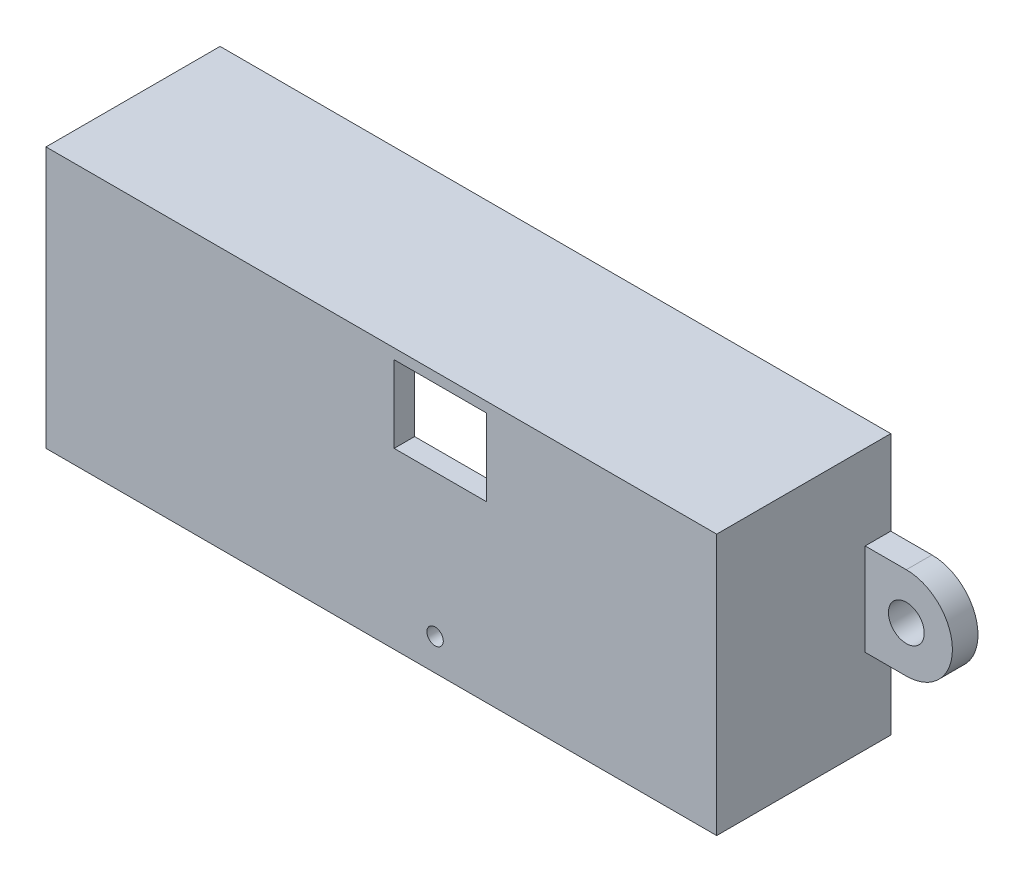
SolidWorks part; units mm, degrees
ref_plane "Спереди" through (0, 0, 0) normal (0, 0, 1) x (1, 0, 0)
ref_plane "Сверху" through (0, 0, 0) normal (0, 1, 0) x (1, 0, 0)
ref_plane "Справа" through (0, 0, 0) normal (1, 0, 0) x (0, 0, -1)
sketch "Эскиз1" plane through (0, 0, 0) normal (0, 0, 1) x (1, 0, 0)
  line L5 (0, 0) -> (123, 0)
  line L6 (0, 0) -> (0, 43)
  line L7 (0, 43) -> (123, 43)
  line L8 (123, 0) -> (123, 43)
  dimension "D1" = 123
  dimension "D2" = 43
extrude "Бобышка-Вытянуть1" add sketch "Эскиз1" along normal blind 4
sketch "Эскиз2" plane through (0, 0, 0) normal (0, 0, -1) x (-1, 0, 0)
  line L1 (-127, -4) -> (4, -4)
  line L2 (-127, -4) -> (-127, 47)
  line L3 (-127, 47) -> (4, 47)
  line L4 (4, -4) -> (4, 47)
  line L9 (-123, 0) -> (0, 0)
  line L10 (-123, 0) -> (-123, 43)
  line L11 (-123, 43) -> (0, 43)
  line L12 (0, 0) -> (0, 43)
  dimension "D1" = 4
  dimension "D2" = 4
  dimension "D3" = 4
  dimension "D4" = 4
extrude "Бобышка-Вытянуть2" add sketch "Эскиз2" along normal blind 30 and the other way blind 4
sketch "Эскиз3" plane through (0, 0, -30) normal (0, 0, -1) x (-1, 0, 0)
  line L0 (-127, 12.5) -> (-135.04, 12.5)
  line L1 (-127, 30.5) -> (-135.04, 30.5)
  line L2 (-134.7332, 21.5) -> (-138.54, 21.5) construction
  line L3 (-127, 30.5) -> (-127, 12.5)
  line L4 (-123, 21.5) -> (0, 21.5) construction
  line L5 (-123, 43) -> (-123, 0) construction
  line L6 (0, 0) -> (0, 43) construction
  line L7 (-127, 47) -> (-127, -4) construction
  arc A0 (-135.04, 12.5) -> (-135.04, 30.5) centre (-135.04, 21.5) cw
  circle A1 centre (-135.04, 21.5) radius 3.5
  dimension "D1" = 7
  dimension "D3" = 9
  dimension "D2" = 9
  dimension "D4" = 8.04
extrude "Бобышка-Вытянуть3" add sketch "Эскиз3" against normal blind 5
ref_plane "Плоскость1" through (61.5, 0, 0) normal (1, 0, 0) x (0, 0, -1)
mirror "Зеркальное отражение1" about plane through (61.5, 0, 0) normal (1, 0, 0) of "Бобышка-Вытянуть3"
ref_plane "Плоскость2" through (123, 43, -30) normal (0, 0, -1) x (-1, 0, 0)
sketch "Эскиз5" plane through (0, 0, 4) normal (0, 0, 1) x (1, 0, 0)
  line L1 (82, 30) -> (64, 30)
  line L2 (82, 30) -> (82, 45)
  line L3 (82, 45) -> (64, 45)
  line L4 (64, 30) -> (64, 45)
  circle A0 centre (72, 2.2) radius 1.6
  dimension "D5" = 3.2
  dimension "D1" = 45
  dimension "D2" = 2
  dimension "D3" = 18
  dimension "D4" = 15
  dimension "D6" = 55
  dimension "D7" = 6.2
extrude "Вырез-Вытянуть1" cut sketch "Эскиз5" against normal blind 10
sketch "Эскиз6" plane through (-4, 0, 0) normal (-1, 0, 0) x (0, 0, 1)
  line L0 (-20, 17.3) -> (-22.5, 17.3)
  line L6 (-24.5, 9.65) -> (-24.5, 16.65)
  line L8 (-20, 9) -> (-20, 17.3)
  line L9 (-22.5, 17.3) -> (-22.5, 16.65)
  line L10 (-22.5, 16.65) -> (-24.5, 16.65)
  line L11 (-20, 9) -> (-22.5, 9)
  line L12 (-22.5, 9) -> (-22.5, 9.65)
  line L13 (-22.5, 9.65) -> (-24.5, 9.65)
  line L17 (4, -4) -> (-30, -4) construction
  line L18 (-30, -4) -> (-30, 12.5) construction
  dimension "D1" = 7
  dimension "D2" = 8.3
  dimension "D3" = 4.5
  dimension "D4" = 2.5
  dimension "D5" = 13
  dimension "D6" = 5.5
extrude "Вырез-Вытянуть2" cut sketch "Эскиз6" against normal blind 10
